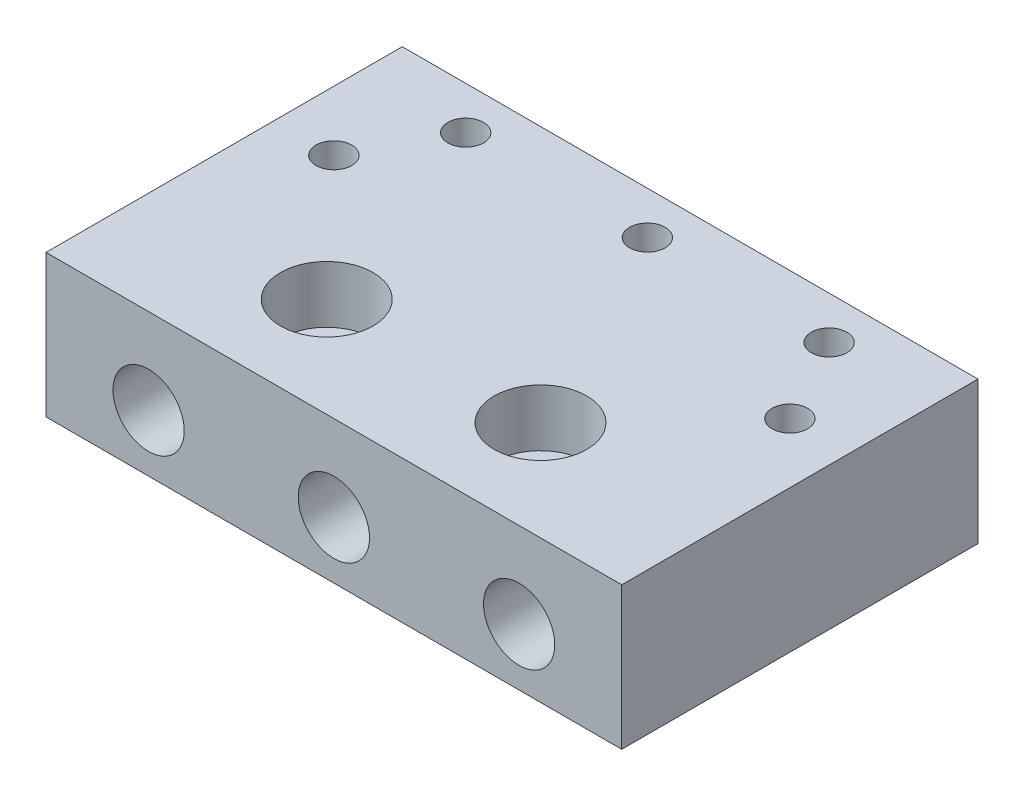
SolidWorks part; units mm, degrees
ref_plane "Front Plane" through (0, 0, 0) normal (0, 0, 1) x (1, 0, 0)
ref_plane "Top Plane" through (0, 0, 0) normal (0, 1, 0) x (1, 0, 0)
ref_plane "Right Plane" through (0, 0, 0) normal (1, 0, 0) x (0, 0, -1)
sketch "Sketch1" plane through (0, 0, 0) normal (0, 0, 1) x (1, 0, 0)
  line L0 (-13, 0) -> (13, 0) construction
  line L1 (0, -8) -> (0, 8) construction
  line L2 (-20.2, 6) -> (-20.2, -4)
  line L3 (-20.2, -4) -> (20.2, -4)
  line L4 (20.2, -4) -> (20.2, 6)
  line L5 (20.2, 6) -> (-20.2, 6)
  circle A0 centre (0, 0) radius 2.5
  circle A1 centre (13, 0) radius 2.5
  circle A2 centre (-13, 0) radius 2.5
  dimension "D3" = 2.5
  dimension "D1" = 40.4
  dimension "D2" = 13
  dimension "D4" = 6
  dimension "D5" = 4
extrude "Boss-Extrude1" add sketch "Sketch1" along normal blind 25
sketch "Sketch2" plane through (0, 6, 0) normal (0, 1, 0) x (1, 0, 0)
  line L0 (-7.5, -9) -> (7.5, -9) construction
  line L1 (0, 0) -> (0, -9) construction
  line L3 (-7.5, -18) -> (7.5, -18) construction
  line L5 (20.2, -25) -> (-20.2, -25) construction
  circle A0 centre (-7.5, -9) radius 1.25 construction
  circle A1 centre (7.5, -9) radius 1.25 construction
  circle A2 centre (7.5, -18) radius 1.55
  circle A3 centre (-7.5, -18) radius 1.55
  circle A4 centre (-17.0788, -4.1649) radius 1.25 construction
  circle A5 centre (17.0788, -4.1649) radius 1.25 construction
  dimension "D1" = 2.5
  dimension "D3" = 3.1
  dimension "D2" = 15
  dimension "D4" = 9
  dimension "D5" = 17.75
  dimension "D6" = 17.75
  dimension "D7" = 7
extrude "Cut-Extrude1" cut sketch "Sketch2" against normal through all
sketch "Sketch3" plane through (0, 6, 0) normal (0, 1, 0) x (1, 0, 0)
  line L0 (-12.75, -3) -> (12.75, -3) construction
  circle A0 centre (0, -3) radius 1.25
  circle A1 centre (-12.75, -3) radius 1.25
  circle A2 centre (12.75, -3) radius 1.25
  dimension "D1" = 2.5
  dimension "D2" = 12.75
  dimension "D3" = 3
extrude "Cut-Extrude2" cut sketch "Sketch3" against normal up to next
sketch "Sketch4" plane through (0, 6, 0) normal (0, 1, 0) x (1, 0, 0)
  line L0 (0, 0) -> (0, -9) construction
  line L1 (16, -9) -> (-16, -9) construction
  line L2 (20.2, 0) -> (-20.2, 0) construction
  circle A0 centre (-16, -9) radius 1.25
  circle A1 centre (16, -9) radius 1.25
  dimension "D1" = 2.5
  dimension "D3" = 32
  dimension "D2" = 9
extrude "Cut-Extrude3" cut sketch "Sketch4" against normal blind 4
chamfer "Chamfer1" distance 1.25 angle 35.5 2 edges at (-17.25, 2, 9) (14.75, 2, 9)
sketch "Sketch5" plane through (0, 6, 0) normal (0, 1, 0) x (1, 0, 0)
  circle A0 centre (7.5, -18) radius 3.25
  circle A1 centre (-7.5, -18) radius 3.25
  circle A2 centre (7.5, -18) radius 1.55 construction
  circle A3 centre (-7.5, -18) radius 1.55 construction
  dimension "D1" = 6.5
extrude "Cut-Extrude4" cut sketch "Sketch5" against normal blind 4
equation "\"D6@Sketch2\"=\"D5@Sketch2\""
